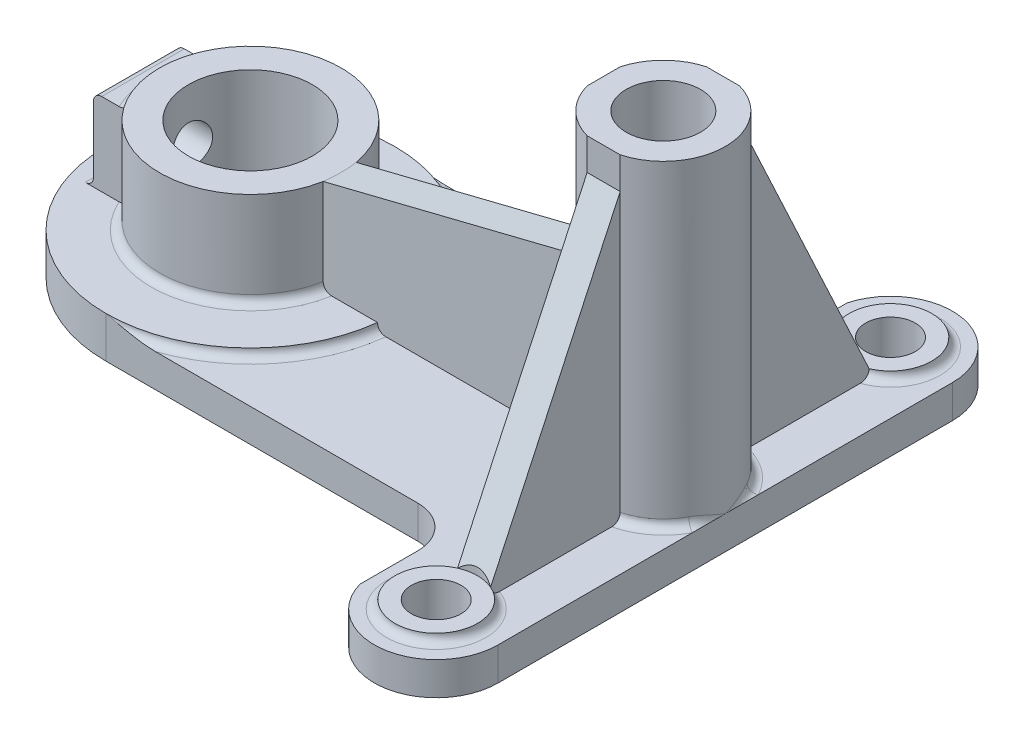
SolidWorks part; units mm, degrees
ref_plane "Piano frontale" through (0, 0, 0) normal (0, 0, 1) x (1, 0, 0)
ref_plane "Piano superiore" through (0, 0, 0) normal (0, 1, 0) x (1, 0, 0)
ref_plane "Piano destro" through (0, 0, 0) normal (1, 0, 0) x (0, 0, -1)
sketch "Schizzo1" plane through (0, 0, 0) normal (0, 1, 0) x (1, 0, 0)
  line L0 (0, 35) -> (85.5432, 35)
  line L1 (-70.3617, 0) -> (147.3858, 0) construction
  line L2 (100, 55) -> (100, -55) construction
  line L3 (115, 55) -> (115, -55)
  line L4 (85.5432, 59) -> (85.5432, 35)
  line L5 (96, 45.8348) -> (96, 14.4568)
  line L6 (100, 96.3393) -> (100, -87.1626) construction
  line L7 (104, 45.8348) -> (104, 14.4568)
  line L8 (96, -14.4568) -> (96, -45.8348)
  line L9 (104, -14.4568) -> (104, -45.8348)
  line L10 (0, -35) -> (85.5432, -35)
  line L11 (-19.5959, 10) -> (-28, 10)
  line L12 (-28, 10) -> (-28, -10)
  line L13 (-19.5959, -10) -> (-28, -10)
  line L14 (0, 42.2968) -> (0, -45.7744) construction
  line L15 (85.5432, 4) -> (21.6333, 4)
  line L16 (85.5432, -4) -> (21.6333, -4)
  line L18 (85.5432, -35) -> (85.5432, -59)
  circle A0 centre (0, 0) radius 15
  circle A1 centre (0, 0) radius 22
  arc A2 (34.7707, 4) -> (34.7707, -4) centre (0, 0) ccw
  arc A3 (115, 55) -> (85.5432, 59) centre (100, 55) ccw
  arc A4 (85.5432, -59) -> (115, -55) centre (100, -55) ccw
  circle A5 centre (100, 55) radius 10
  circle A6 centre (100, 55) radius 6
  circle A7 centre (100, 0) radius 15
  circle A8 centre (100, 0) radius 9
  circle A9 centre (100, -55) radius 10
  circle A10 centre (100, -55) radius 6
  point P11 (100, 0)
  point P35 (0, 0)
  point P37 (0, 0)
  point P39 (0, 0)
  point P40 (0, 0)
  point P45 (-28, 0)
  point P52 (0, 0)
  point P54 (0, 0)
  point P55 (0, 0)
  point P56 (0, 0)
  point P57 (0, 0)
  point P58 (0, 0)
  dimension "D1" = 70
  dimension "D2" = 44
  dimension "D3" = 30
  dimension "D9" = 20
  dimension "D10" = 15
  dimension "D11" = 12
  dimension "D12" = 20
  dimension "D13" = 18
  dimension "D14" = 12
  dimension "D15" = 30
  dimension "D18" = 15
  dimension "D4" = 20
  dimension "D5" = 28
  dimension "D6" = 100
  dimension "D7" = 8
  dimension "D8" = 110
  dimension "D16" = 8
  dimension "D17" = 4
  dimension "D19" = 24
  dimension "D20" = 110
extrude "Estrusione-Estrusione1" add sketch "Schizzo1" along normal blind 33 contours A1 A0 region at (21.2885, 0, -1.9516)
extrude "Estrusione-Estrusione2" add sketch "Schizzo1<4>" along normal blind 30 contours A1 L11 L12 L13 region at (-24.5713, 0, 0)
sketch "Schizzo1<4>" plane through (0, 0, 0) normal (0, 1, 0) x (1, 0, 0) same geometry as "Schizzo1"
extrude "Estrusione-Estrusione3" add sketch "Schizzo1<5>" along normal blind 10 contours A2 L16 A1 L13 L12 L11 L15 | A9 A10 | A5 A6 region at (22.6339, 0, -25.387) region at (94.6777, 0, -63.13) region at (100, 0, 45.2828)
sketch "Schizzo1<5>" plane through (0, 0, 0) normal (0, 1, 0) x (1, 0, 0) same geometry as "Schizzo1"
extrude "Estrusione-Estrusione7" add sketch "Schizzo1<8>" along normal blind 85 contours A7 L3 A8 | A7 L15 A1 L16 | A7 L7 A5 L5 | A9 L9 A7 L8 region at (53.5291, 0, 0) region at (89.6934, 0, -10.3066) region at (100, 0, -30.0474) region at (100, 0, 30.0474)
sketch "Schizzo1<8>" plane through (0, 0, 0) normal (0, 1, 0) x (1, 0, 0) same geometry as "Schizzo1"
extrude "Estrusione-Estrusione8" add sketch "Schizzo1<9>" along normal blind 8 contours A7 L3 A3 L4 L0 A2 L15 L5 A5 L7 | A9 L8 A7 L16 A2 L10 L18 A4 L3 L9 region at (72.0132, 0, -26.6313) region at (72.0132, 0, 26.6313)
sketch "Schizzo1<9>" plane through (0, 0, 0) normal (0, 1, 0) x (1, 0, 0) same geometry as "Schizzo1"
fillet "Raccordo1" radius 2 9 edges at (3.1682, 10, -21.7707) (3.1682, 10, 21.7707) (23.2916, 8, -26.1247) (23.2916, 8, 26.1247) (-28, 10, 0) (-28, 30, 0) (-22, 30, 0) (100, 8, 65) (100, 8, -65)
fillet "Raccordo2" radius 10 2 edges at (85.5432, 4, -35) (85.5432, 4, 35)
ref_plane "Piano1" through (100, 0, 0) normal (1, 0, 0) x (0, 0, -1)
sketch "Schizzo4" plane through (104, 0, 0) normal (1, 0, 0) x (0, 0, -1)
  line L0 (-45.8348, 10) -> (-14.4568, 77.2904)
  line L1 (-14.4568, 85) -> (-14.4568, 8) construction
  line L2 (-14.4568, 8) -> (-43.6863, 8) construction
  line L3 (0, 114.6079) -> (0, -37.6561) construction
  line L4 (45.8348, 10) -> (14.4568, 77.2904)
  line L5 (65, 10) -> (45.8348, 10) construction
  line L6 (-14.4568, 77.2904) -> (-14.4568, 85)
  line L7 (-14.4568, 85) -> (-45.8348, 85)
  line L8 (-45.8348, 85) -> (-45.8348, 10)
  line L9 (14.4568, 77.2904) -> (14.4568, 85)
  line L10 (14.4568, 85) -> (45.8348, 85)
  line L11 (45.8348, 85) -> (45.8348, 10)
  dimension "D1" = 65
extrude "Taglio-Estrusione1" cut sketch "Schizzo4" against normal up to next and the other way through all
sketch "Schizzo7" plane through (0, 0, 0) normal (0, 0, 1) x (1, 0, 0)
  line L0 (21.6333, 33) -> (21.6333, 85)
  line L1 (21.6333, 85) -> (85.5432, 85)
  line L2 (85.5432, 85) -> (85.5432, 48.9345)
  line L3 (85.5432, 85) -> (85.5432, 8) construction
  line L4 (85.5432, 48.9345) -> (21.6333, 33)
  line L5 (85.5432, 8) -> (36.7831, 8) construction
  dimension "D1" = 14
extrude "Taglio-Estrusione4" cut sketch "Schizzo7" against normal through all both and the other way through all
fillet "Raccordo3" radius 2 4 edges at (89.3934, 8, -10.6066) (111.9373, 8, -9.083) (111.9373, 8, 9.083) (89.3934, 8, 10.6066)
hole_wizard "Foro Ø10.0 (10)-1" positions "Schizzo8" profile "Schizzo9" hole size "Ø10.0" standard "ISO" end condition up to next
sketch "Schizzo8" plane through (-28, 0, 0) normal (-1, 0, 0) x (0, 0, 1)
  line L0 (0, 0) -> (0, 43.7824) construction
  line L2 (-10, 20) -> (10, 20) construction
  line L3 (-10, 32) -> (-10, 12) construction
  line L4 (10, 28) -> (10, 12) construction
  line L6 (-35, 0) -> (35, 0) construction
  point P16 (0, 20)
  dimension "D1" = 20
sketch "Schizzo9" plane through (-28, 20, 0) normal (0, 1, 0) x (0, 0, 1)
  line L0 (0, 0) -> (0, 13)
  line L1 (0, 13) -> (5, 13)
  line L2 (5, 13) -> (5, 0)
  line L5 (5, 0) -> (0, 0)
  line L11 (0, -6.35) -> (0, 107.95) construction
  dimension "Thru Hole Dia." = 10
  dimension "Thru Hole Depth" = 13
